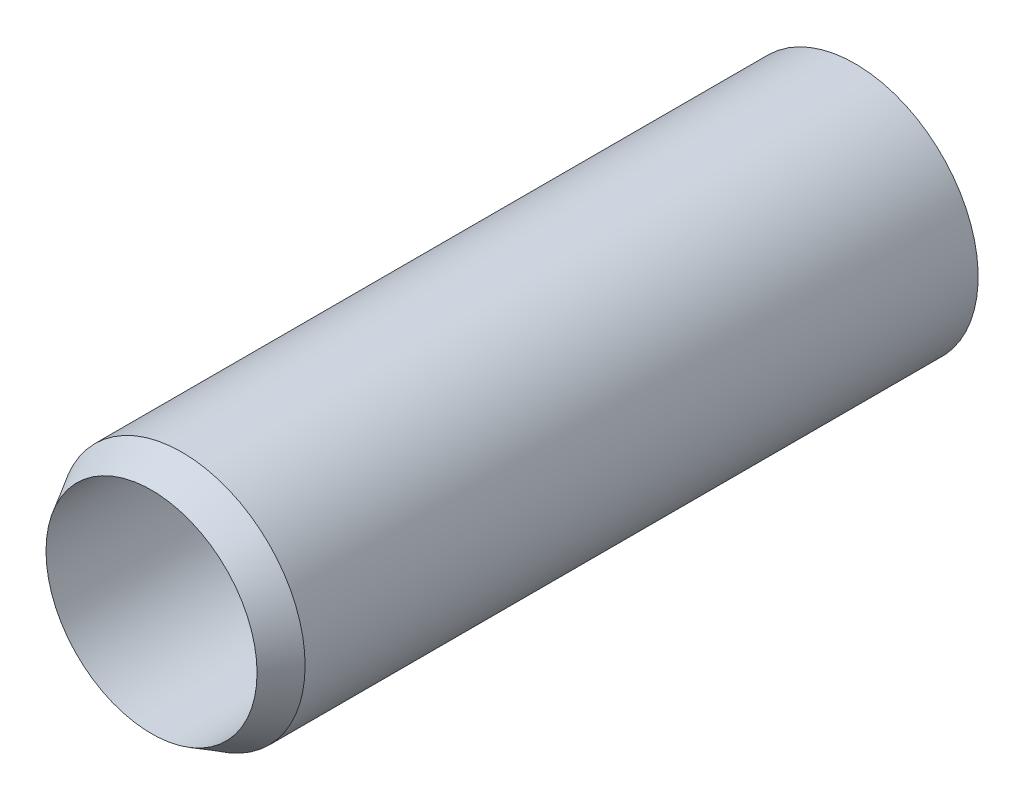
SolidWorks part; units mm, degrees
ref_plane "Front Plane" through (0, 0, 0) normal (0, 0, 1) x (1, 0, 0)
ref_plane "Top Plane" through (0, 0, 0) normal (0, 1, 0) x (1, 0, 0)
ref_plane "Right Plane" through (0, 0, 0) normal (1, 0, 0) x (0, 0, -1)
ref_plane "Plane1" through (0, 3.7931, 0) normal (0, -1, 0) x (1, 0, 0)
sketch "Sketch1" plane through (0, 3.7931, 0) normal (0, -1, 0) x (1, 0, 0)
  line L0 (-13.1201, 20) -> (-13.6201, 20)
  line L1 (-13.6201, 20) -> (-13.6201, 0)
  line L2 (-13.6201, 0) -> (-13.1201, 0)
  line L3 (-13.1201, 0) -> (-13.1201, 20)
  line L4 (-16.6201, 20) -> (-16.6201, 0) construction
  dimension "D1" = 3.5
  dimension "D2" = 0.5
revolve "Revolve1" add sketch "Sketch1" angle 360 about L4 reverse direction yes
chamfer "Chamfer1" distance 0.5 angle 60 1 edges at (-20.1201, 3.7931, 20) first distance on face at (-19.6201, 3.7931, 20)
